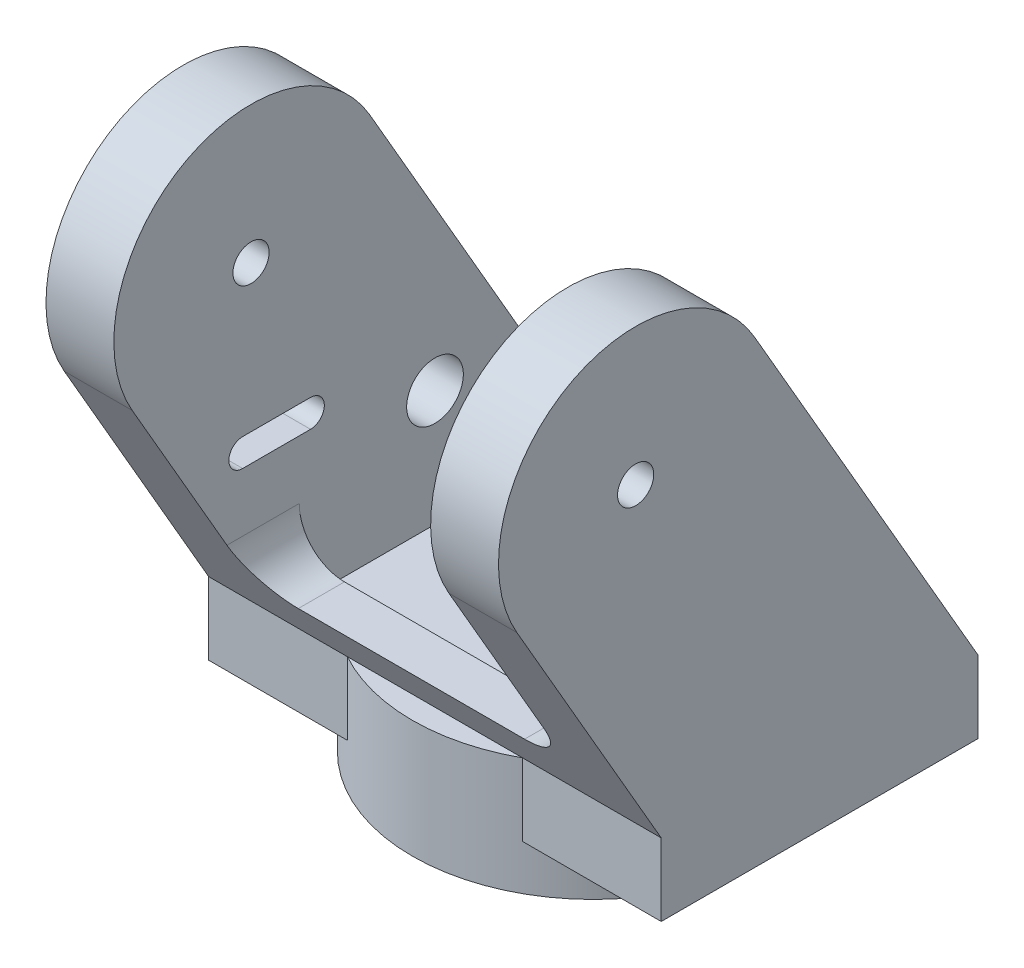
SolidWorks part; units mm, degrees
ref_plane "Front Plane" through (0, 0, 0) normal (0, 0, 1) x (1, 0, 0)
ref_plane "Top Plane" through (0, 0, 0) normal (0, 1, 0) x (1, 0, 0)
ref_plane "Right Plane" through (0, 0, 0) normal (1, 0, 0) x (0, 0, -1)
sketch "Sketch1" plane through (0, 0, 0) normal (0, 1, 0) x (1, 0, 0)
  circle A0 centre (0, 0) radius 40
  dimension "D1" = 80
extrude "Boss-Extrude2" add sketch "Sketch1" along normal blind 26
sketch "Sketch3" plane through (0, 0, 0) normal (0, -1, 0) x (1, 0, 0)
  circle A0 centre (0, 0) radius 23.5
  dimension "D1" = 47
extrude "Cut-Extrude1" cut sketch "Sketch3" against normal blind 5
sketch "Sketch4" plane through (0, 5, 0) normal (0, -1, 0) x (1, 0, 0)
  line L0 (0, 0) -> (52.6799, 0) construction
  circle A0 centre (0, 0) radius 17.5 construction
  circle A1 centre (12, 0) radius 1.5
  circle A2 centre (0, -12) radius 1.5
  circle A3 centre (-12, 0) radius 1.5
  circle A4 centre (0, 12) radius 1.5
  point P15 (0, 0)
  dimension "D1" = 35
  dimension "D2" = 3
  dimension "D3" = 12
  dimension "D4" = 4
sketch "Sketch5" plane through (0, 5, 0) normal (0, -1, 0) x (1, 0, 0)
  circle A0 centre (0, 0) radius 8.75
  dimension "D1" = 17.5
sketch "Sketch7" plane through (0, 0, 0) normal (1, 0, 0) x (0, 0, -1)
  line L0 (0, 0) -> (0, 36) construction
  line L1 (40, 26) -> (-40, 26) construction
  line L2 (-35, 26) -> (35, 26)
  line L3 (-35, 26) -> (-35, 10)
  line L4 (-35, 10) -> (35, 10)
  line L5 (35, 26) -> (35, 10)
  line L6 (0, 10) -> (0, 26) construction
  line L7 (-35, 18) -> (35, 18) construction
  line L8 (-40, 26) -> (-40, 0) construction
  point P3 (0, 18)
  dimension "D1" = 0
  dimension "D2" = 5
  dimension "D3" = 8
  dimension "D4" = 5
extrude "Boss-Extrude4" add sketch "Sketch7" along normal blind 35 and the other way blind 35
extrude "Cut-Extrude9" cut sketch "Sketch5" against normal blind 10
sketch "Sketch10" plane through (0, 15, 0) normal (0, -1, 0) x (1, 0, 0)
  circle A0 centre (0, 0) radius 4
  dimension "D1" = 8
extrude "Cut-Extrude10" cut sketch "Sketch10" against normal blind 9.4
sketch "Sketch16" plane through (-35, 0, 0) normal (-1, 0, 0) x (0, 0, 1)
  line L0 (-35, 10) -> (-35, 26)
  line L1 (-35, 26) -> (14.4003, 111.5639)
  line L4 (35, 26) -> (35, 10)
  line L5 (35, 10) -> (-35, 10)
  line L6 (-35, 26) -> (-19.3649, 26) construction
  line L7 (0, 0) -> (0, 102.8) construction
  line L8 (14.4003, 111.5639) -> (66.9003, 81.253) construction
  line L9 (66.9003, 81.253) -> (35, 26)
  line L10 (19.3649, 26) -> (-19.3649, 26) construction
  line L11 (0, 61) -> (75.7383, 61) construction
  line L13 (27.5, 61) -> (42.5, 61) construction
  line L14 (27.5, 64.05) -> (42.5, 64.05)
  line L15 (27.5, 57.95) -> (42.5, 57.95)
  line L16 (19.3649, 26) -> (35, 26) construction
  arc A1 (14.4003, 111.5639) -> (66.9003, 81.253) centre (40.6503, 96.4085) cw
  circle A2 centre (0, 44.6) radius 18.6 construction
  circle A3 centre (0, 51.6) radius 6.265
  arc A4 (27.5, 64.05) -> (27.5, 57.95) centre (27.5, 61) ccw
  arc A5 (42.5, 57.95) -> (42.5, 64.05) centre (42.5, 61) ccw
  point P17 (0, 26)
  point P27 (35, 61)
  dimension "D3" = 0
  dimension "D2" = 37.2
  dimension "D4" = 12.53
  dimension "D1" = 60
  dimension "D5" = 90
  dimension "D6" = 7
  dimension "D7" = 60.5
  dimension "D8" = 35
  dimension "D9" = 15
  dimension "D10" = 6.1
  dimension "D11" = 35
extrude "Boss-Extrude5" add sketch "Sketch16" along normal blind 15
mirror "Mirror1" about plane through (0, 0, 0) normal (1, 0, 0) of "Boss-Extrude5"
sketch "Sketch18" plane through (-50, 0, 0) normal (-1, 0, 0) x (0, 0, 1)
  circle A0 centre (40.6503, 96.4085) radius 4
  dimension "D1" = 8
extrude "Cut-Extrude12" cut sketch "Sketch18" against normal through all
sketch "Sketch24" plane through (-35, 0, 0) normal (1, 0, 0) x (0, 0, -1)
  line L0 (-40.1962, 35) -> (-30, 35)
  line L1 (-35, 26) -> (-66.9003, 81.253) construction
  line L4 (-35, 26) -> (-40.1962, 35)
  line L5 (-30, 35) -> (-30, 26)
  line L6 (-30, 26) -> (-35, 26)
  dimension "D1" = 9
  dimension "D2" = 5
extrude "Boss-Extrude9" add sketch "Sketch24" along normal through all
fillet "Fillet4" radius 10 1 edges at (-35, 35, 35.0981)
fillet "Fillet5" radius 10 1 edges at (35, 35, 35.0981)
extrude "Cut-Extrude15" cut sketch "Sketch4" against normal blind 8
sketch "Sketch25" plane through (35, 0, 0) normal (-1, 0, 0) x (0, 0, 1)
  circle A0 centre (0, 51.6) radius 6.265
  circle A1 centre (0, 51.6) radius 6.265 construction
  dimension "D1" = 0
  dimension "D2" = 0
extrude "Boss-Extrude10" add sketch "Sketch25" against normal blind 15
sketch "Sketch26" plane through (35, 0, 0) normal (-1, 0, 0) x (0, 0, 1)
  line L0 (27.5, 61) -> (42.5, 61) construction
  line L1 (27.5, 64.05) -> (42.5, 64.05)
  line L2 (27.5, 57.95) -> (42.5, 57.95)
  line L3 (42.5, 64.05) -> (27.5, 64.05) construction
  arc A0 (27.5, 64.05) -> (27.5, 57.95) centre (27.5, 61) ccw
  arc A1 (42.5, 57.95) -> (42.5, 64.05) centre (42.5, 61) ccw
  arc A2 (27.5, 64.05) -> (27.5, 57.95) centre (27.5, 61) ccw construction
  arc A3 (42.5, 57.95) -> (42.5, 64.05) centre (42.5, 61) ccw construction
  point P2 (35, 61)
  dimension "D1" = 0
  dimension "D3" = 0
  dimension "D2" = 0
  dimension "D4" = 6.1
extrude "Boss-Extrude11" add sketch "Sketch26" against normal blind 15
